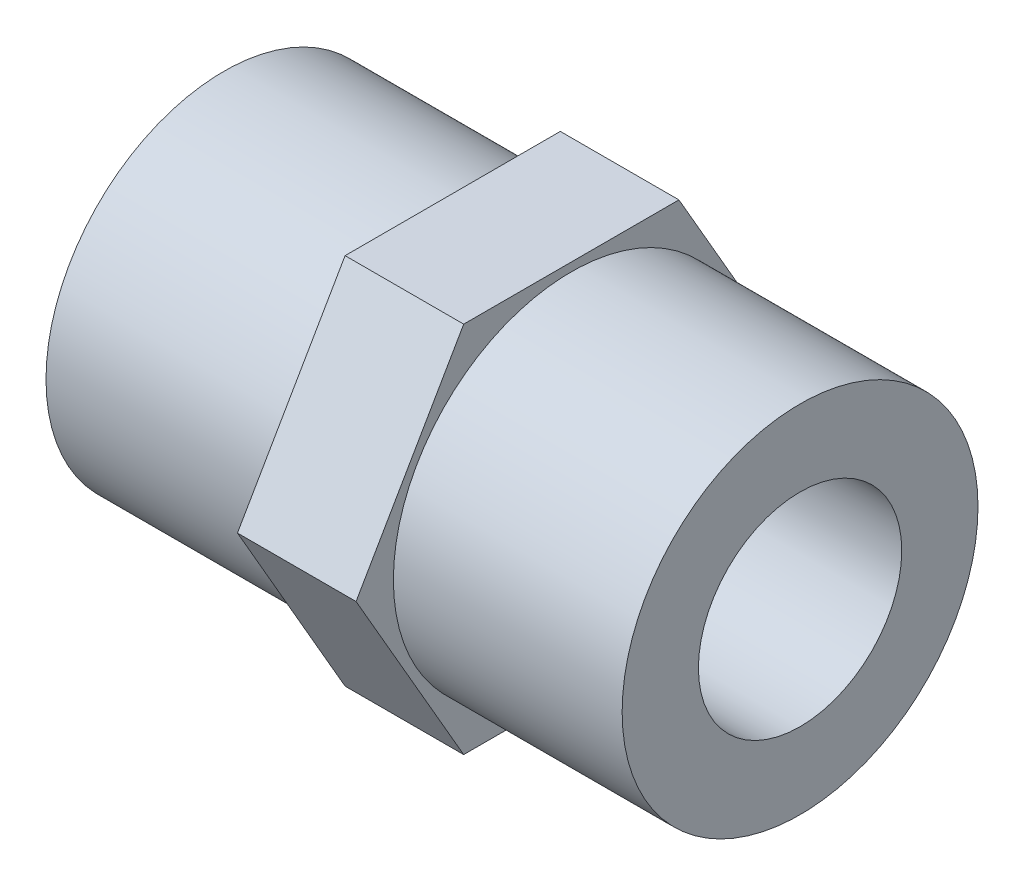
SolidWorks part; units mm, degrees
material "Acciaio inossidabile fuso"
ref_plane "Piano frontale" through (0, 0, 0) normal (0, 0, 1) x (1, 0, 0)
ref_plane "Piano superiore" through (0, 0, 0) normal (0, 1, 0) x (1, 0, 0)
ref_plane "Piano destro" through (0, 0, 0) normal (1, 0, 0) x (0, 0, -1)
sketch "Schizzo1" plane through (0, 0, 0) normal (0, 0, 1) x (1, 0, 0)
  line L0 (0, 0) -> (42.6268, 0) construction
  line L1 (0, 6) -> (0, 10.5)
  line L2 (0, 10.5) -> (13.5, 10.5)
  line L3 (13.5, 10.5) -> (13.5, 11)
  line L4 (13.5, 11) -> (20.5, 11)
  line L5 (20.5, 11) -> (20.5, 10.5)
  line L6 (20.5, 10.5) -> (34, 10.5)
  line L7 (34, 10.5) -> (34, 6)
  line L8 (34, 6) -> (0, 6)
  dimension "D1" = 13.5
  dimension "D2" = 12
  dimension "D3" = 21
  dimension "D4" = 34
  dimension "D5" = 22
revolve "Rivoluzione1" add sketch "Schizzo1" angle 360 about L0
sketch "Schizzo2" plane through (20.5, 0, 0) normal (1, 0, 0) x (0, 0, -1)
  line L0 (-12.7017, 0) -> (-6.3509, -11)
  line L1 (-6.3509, -11) -> (6.3509, -11)
  line L2 (6.3509, -11) -> (12.7017, 0)
  line L3 (12.7017, 0) -> (6.3509, 11)
  line L4 (6.3509, 11) -> (-6.3509, 11)
  line L5 (-6.3509, 11) -> (-12.7017, 0)
  circle A0 centre (0, 0) radius 11 construction
  circle A1 centre (0, 0) radius 11
  circle M7 centre (0, 0) radius 11
extrude "Estrusione-Estrusione1" add sketch "Schizzo2" against normal up to surface (7 mm away) contours L5 L0 M7 | L4 L5 M7 | L3 L4 M7 | L0 L1 M7 | L1 L2 M7 | L2 L3 M7 region at (20.5, 0, 11.3692) region at (20.5, -9.846, 5.6846) region at (20.5, 9.846, 5.6846) region at (20.5, -9.846, -5.6846) region at (20.5, 9.846, -5.6846) region at (20.5, 0, -11.3692) up to face at (13.5, 0, 10.5)
